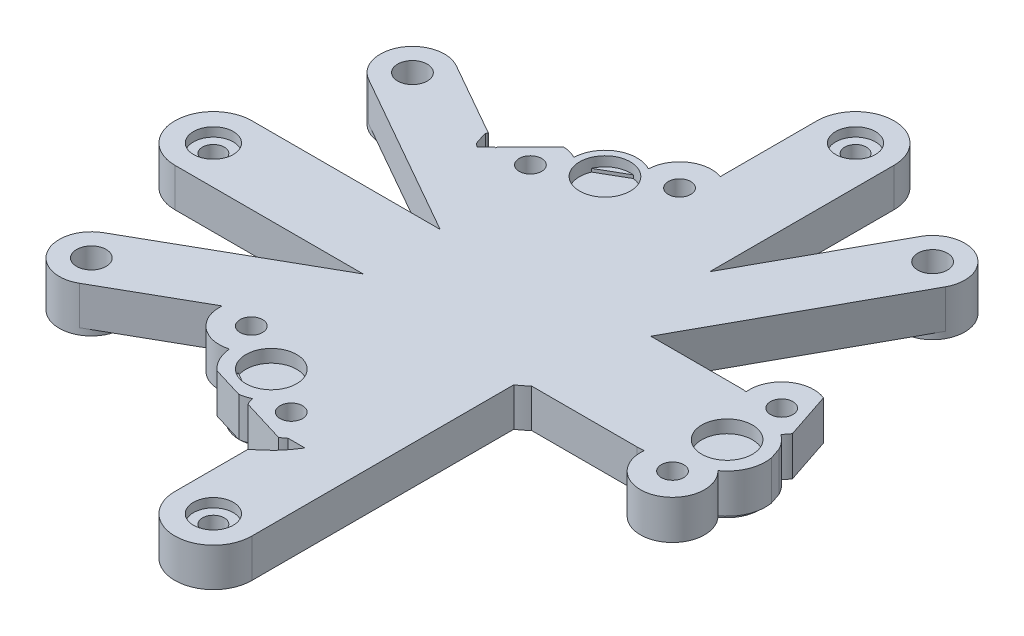
SolidWorks part; units mm, degrees
other "Fixed Star Plate Left"
ref_plane "Front Plane" through (0, 0, 0) normal (0, 0, 1) x (1, 0, 0)
ref_plane "Top Plane" through (0, 0, 0) normal (0, 1, 0) x (1, 0, 0)
ref_plane "Right Plane" through (0, 0, 0) normal (1, 0, 0) x (0, 0, -1)
sketch3d "Base Outline Sketch datum points"
  point P0 (0, 71, 0)
  point P1 (10, 71, 0)
  point P2 (0, 71, -10)
ref_plane "Base Outline Sketch plane" through (0, 71, 0) normal (0, 1, 0) x (1, 0, 0)
sketch "Base Outline Sketch" plane through (0, 71, 0) normal (0, 1, 0) x (1, 0, 0)
  line L0 (-32.2917, 8) -> (-46.1853, 8)
  line L1 (-24.4227, 13.1376) -> (-22.0154, 5.909)
  line L2 (-20.9711, 2.7735) -> (-20.3706, 0.9703)
  line L3 (-48.7418, -8) -> (-32.2917, -8)
  line L4 (-50.2917, -50) -> (-50.2917, -9.2195)
  line L5 (-62.2917, -38.6002) -> (-62.2917, -50)
  line L6 (-58.0273, -34) -> (-60.6452, -34)
  line L7 (-61.5389, -34.6217) -> (-68.3642, -32.542)
  line L8 (-70.4166, -31.9166) -> (-75.3281, -30.42)
  line L9 (-97.8216, -29.3473) -> (-83.633, -21.2856)
  line L10 (-76.9729, -6) -> (-102.7617, -20.6527)
  line L11 (-106.2917, -6) -> (-76.9729, -6)
  line L12 (-76.9729, 6) -> (-106.2917, 6)
  line L13 (-102.7617, 20.6527) -> (-76.9729, 6)
  line L14 (-86.2562, 22.776) -> (-97.8216, 29.3473)
  line L15 (-86.2562, 22.776) -> (-86.3054, 22.6772)
  line L16 (-86.3054, 22.6772) -> (-86.3838, 22.4486)
  line L17 (-85.7572, 20.4132) -> (-85.2034, 19.9887)
  line L18 (-85.2034, 19.9887) -> (-83.8108, 21.3866)
  line L19 (-83.633, 21.2856) -> (-83.8108, 21.3866)
  line L20 (-83.6495, 21.5484) -> (-78.4893, 26.7281)
  line L21 (-62.2917, 50) -> (-62.2917, 34.9546)
  line L22 (-50.2917, 21.2843) -> (-50.2917, 50)
  line L23 (-38.6727, 42.4096) -> (-50.2917, 21.2843)
  line L24 (-46.1853, 8) -> (-29.9106, 37.5904)
  circle A0 centre (-71.2917, -25.9808) radius 3.95
  circle A1 centre (-63.9304, -30.2308) radius 1.75
  circle A2 centre (-26.2917, 0) radius 3.95
  circle A3 centre (-56.2917, -50) radius 3.1
  circle A4 centre (-26.2917, -8.5) radius 1.75
  circle A5 centre (-78.6529, -21.7308) radius 1.75
  circle A6 centre (-100.2917, -25) radius 2.3
  circle A7 centre (-71.2917, 25.9808) radius 3.95
  circle A8 centre (-34.2917, 40) radius 2.3
  circle A9 centre (-26.2917, 8.5) radius 1.75
  circle A10 centre (-63.9304, 30.2308) radius 1.75
  circle A11 centre (-56.2917, 50) radius 3.1
  circle A12 centre (-78.6529, 21.7308) radius 1.75
  circle A13 centre (-106.2917, 0) radius 3.1
  circle A14 centre (-100.2917, 25) radius 2.3
  arc A15 (-31.2594, 7.9331) -> (-32.2917, 8) centre (-32.2917, 0) ccw
  arc A16 (-24.4227, 13.1376) -> (-31.2594, 7.9331) centre (-26.2917, 8.5) ccw
  arc A17 (-22.8248, 4.8971) -> (-22.0154, 5.909) centre (-26.2917, 8.5) ccw
  arc A18 (-20.9711, 2.7735) -> (-22.8248, 4.8971) centre (-26.2917, 0) ccw
  arc A19 (-22.8248, -4.8971) -> (-20.3706, 0.9703) centre (-26.2917, 0) ccw
  arc A20 (-31.2594, -7.9331) -> (-22.8248, -4.8971) centre (-26.2917, -8.5) ccw
  arc A21 (-32.2917, -8) -> (-31.2594, -7.9331) centre (-32.2917, 0) ccw
  arc A22 (-50.2917, -9.2195) -> (-48.7418, -8) centre (-56.2917, 0) ccw
  arc A23 (-62.2917, -50) -> (-50.2917, -50) centre (-56.2917, -50) ccw
  arc A24 (-62.2917, -38.6002) -> (-58.0273, -34) centre (-71.2917, -25.9808) ccw
  arc A25 (-61.5389, -34.6217) -> (-60.6452, -34) centre (-63.9304, -30.2308) ccw
  arc A26 (-68.7841, -31.4316) -> (-68.3642, -32.542) centre (-63.9304, -30.2308) ccw
  arc A27 (-70.4166, -31.9166) -> (-68.7841, -31.4316) centre (-71.2917, -25.9808) ccw
  arc A28 (-77.266, -26.5346) -> (-75.3281, -30.42) centre (-71.2917, -25.9808) ccw
  arc A29 (-83.633, -21.2856) -> (-77.266, -26.5346) centre (-78.6529, -21.7308) ccw
  arc A30 (-100.2917, -30) -> (-97.8216, -29.3473) centre (-100.2917, -25) ccw
  arc A31 (-102.7617, -20.6527) -> (-100.2917, -30) centre (-100.2917, -25) ccw
  arc A32 (-106.2917, 6) -> (-106.2917, -6) centre (-106.2917, 0) ccw
  arc A33 (-97.8216, 29.3473) -> (-102.7617, 20.6527) centre (-100.2917, 25) ccw
  arc A34 (-86.3838, 22.4486) -> (-85.7572, 20.4132) centre (-71.2917, 25.9808) ccw
  arc A35 (-83.6495, 21.5484) -> (-83.633, 21.2856) centre (-78.6529, 21.7308) ccw
  arc A36 (-76.2892, 26.1368) -> (-78.4893, 26.7281) centre (-78.6529, 21.7308) ccw
  arc A37 (-68.928, 30.3868) -> (-76.2892, 26.1368) centre (-71.2917, 25.9808) ccw
  arc A38 (-68.7841, 31.4316) -> (-68.928, 30.3868) centre (-63.9304, 30.2308) ccw
  arc A39 (-62.2917, 34.9546) -> (-68.7841, 31.4316) centre (-63.9304, 30.2308) ccw
  arc A40 (-50.2917, 50) -> (-62.2917, 50) centre (-56.2917, 50) ccw
  arc A41 (-29.9106, 37.5904) -> (-38.6727, 42.4096) centre (-34.2917, 40) ccw
extrude "Base Outline" add sketch "Base Outline Sketch" against normal blind 1.4 separate body
sketch3d "Interface Profile 2 Sketch datum points"
  point P0 (0, 69.6, 0)
  point P1 (10, 69.6, 0)
  point P2 (0, 69.6, -10)
ref_plane "Interface Profile 2 Sketch plane" through (0, 69.6, 0) normal (0, 1, 0) x (1, 0, 0)
sketch "Interface Profile 2 Sketch" plane through (0, 69.6, 0) normal (0, 1, 0) x (1, 0, 0)
  line L0 (-32.2917, 8) -> (-46.1853, 8)
  line L1 (-24.4227, 13.1376) -> (-22.0154, 5.909)
  line L2 (-20.9711, 2.7735) -> (-20.3706, 0.9703)
  line L3 (-48.7418, -8) -> (-32.2917, -8)
  line L4 (-50.2917, -50) -> (-50.2917, -9.2195)
  line L5 (-62.2917, -38.6002) -> (-62.2917, -50)
  line L6 (-58.0273, -34) -> (-60.6452, -34)
  line L7 (-61.5389, -34.6217) -> (-68.3642, -32.542)
  line L8 (-70.4166, -31.9166) -> (-75.3281, -30.42)
  line L9 (-97.8216, -29.3473) -> (-83.633, -21.2856)
  line L10 (-76.9729, -6) -> (-102.7617, -20.6527)
  line L11 (-106.2917, -6) -> (-76.9729, -6)
  line L12 (-76.9729, 6) -> (-106.2917, 6)
  line L13 (-102.7617, 20.6527) -> (-76.9729, 6)
  line L14 (-86.2562, 22.776) -> (-97.8216, 29.3473)
  line L15 (-86.2562, 22.776) -> (-86.3054, 22.6772)
  line L16 (-86.3054, 22.6772) -> (-86.3838, 22.4486)
  line L17 (-85.7572, 20.4132) -> (-85.2034, 19.9887)
  line L18 (-85.2034, 19.9887) -> (-83.8108, 21.3866)
  line L19 (-83.633, 21.2856) -> (-83.8108, 21.3866)
  line L20 (-83.6495, 21.5484) -> (-78.4893, 26.7281)
  line L21 (-62.2917, 50) -> (-62.2917, 34.9546)
  line L22 (-50.2917, 21.2843) -> (-50.2917, 50)
  line L23 (-38.6727, 42.4096) -> (-50.2917, 21.2843)
  line L24 (-46.1853, 8) -> (-29.9106, 37.5904)
  circle A0 centre (-71.2917, -25.9808) radius 3.95
  circle A1 centre (-63.9304, -30.2308) radius 1.75
  circle A2 centre (-26.2917, 0) radius 3.95
  circle A3 centre (-56.2917, -50) radius 1.7
  circle A4 centre (-56.2917, 50) radius 1.7
  circle A5 centre (-106.2917, 0) radius 1.7
  circle A6 centre (-26.2917, -8.5) radius 1.75
  circle A7 centre (-78.6529, -21.7308) radius 1.75
  circle A8 centre (-100.2917, -25) radius 2.3
  circle A9 centre (-71.2917, 25.9808) radius 3.95
  circle A10 centre (-34.2917, 40) radius 2.3
  circle A11 centre (-26.2917, 8.5) radius 1.75
  circle A12 centre (-63.9304, 30.2308) radius 1.75
  circle A13 centre (-78.6529, 21.7308) radius 1.75
  circle A14 centre (-100.2917, 25) radius 2.3
  arc A15 (-31.2594, 7.9331) -> (-32.2917, 8) centre (-32.2917, 0) ccw
  arc A16 (-24.4227, 13.1376) -> (-31.2594, 7.9331) centre (-26.2917, 8.5) ccw
  arc A17 (-22.8248, 4.8971) -> (-22.0154, 5.909) centre (-26.2917, 8.5) ccw
  arc A18 (-20.9711, 2.7735) -> (-22.8248, 4.8971) centre (-26.2917, 0) ccw
  arc A19 (-22.8248, -4.8971) -> (-20.3706, 0.9703) centre (-26.2917, 0) ccw
  arc A20 (-31.2594, -7.9331) -> (-22.8248, -4.8971) centre (-26.2917, -8.5) ccw
  arc A21 (-32.2917, -8) -> (-31.2594, -7.9331) centre (-32.2917, 0) ccw
  arc A22 (-50.2917, -9.2195) -> (-48.7418, -8) centre (-56.2917, 0) ccw
  arc A23 (-62.2917, -50) -> (-50.2917, -50) centre (-56.2917, -50) ccw
  arc A24 (-62.2917, -38.6002) -> (-58.0273, -34) centre (-71.2917, -25.9808) ccw
  arc A25 (-61.5389, -34.6217) -> (-60.6452, -34) centre (-63.9304, -30.2308) ccw
  arc A26 (-68.7841, -31.4316) -> (-68.3642, -32.542) centre (-63.9304, -30.2308) ccw
  arc A27 (-70.4166, -31.9166) -> (-68.7841, -31.4316) centre (-71.2917, -25.9808) ccw
  arc A28 (-77.266, -26.5346) -> (-75.3281, -30.42) centre (-71.2917, -25.9808) ccw
  arc A29 (-83.633, -21.2856) -> (-77.266, -26.5346) centre (-78.6529, -21.7308) ccw
  arc A30 (-100.2917, -30) -> (-97.8216, -29.3473) centre (-100.2917, -25) ccw
  arc A31 (-102.7617, -20.6527) -> (-100.2917, -30) centre (-100.2917, -25) ccw
  arc A32 (-106.2917, 6) -> (-106.2917, -6) centre (-106.2917, 0) ccw
  arc A33 (-97.8216, 29.3473) -> (-102.7617, 20.6527) centre (-100.2917, 25) ccw
  arc A34 (-86.3838, 22.4486) -> (-85.7572, 20.4132) centre (-71.2917, 25.9808) ccw
  arc A35 (-83.6495, 21.5484) -> (-83.633, 21.2856) centre (-78.6529, 21.7308) ccw
  arc A36 (-76.2892, 26.1368) -> (-78.4893, 26.7281) centre (-78.6529, 21.7308) ccw
  arc A37 (-68.928, 30.3868) -> (-76.2892, 26.1368) centre (-71.2917, 25.9808) ccw
  arc A38 (-68.7841, 31.4316) -> (-68.928, 30.3868) centre (-63.9304, 30.2308) ccw
  arc A39 (-62.2917, 34.9546) -> (-68.7841, 31.4316) centre (-63.9304, 30.2308) ccw
  arc A40 (-50.2917, 50) -> (-62.2917, 50) centre (-56.2917, 50) ccw
  arc A41 (-29.9106, 37.5904) -> (-38.6727, 42.4096) centre (-34.2917, 40) ccw
extrude "Interface Profile 2" add sketch "Interface Profile 2 Sketch" against normal blind 0.1
sketch3d "Interface Profile 3 Sketch datum points"
  point P0 (0, 69.5, 0)
  point P1 (10, 69.5, 0)
  point P2 (0, 69.5, -10)
ref_plane "Interface Profile 3 Sketch plane" through (0, 69.5, 0) normal (0, 1, 0) x (1, 0, 0)
sketch "Interface Profile 3 Sketch" plane through (0, 69.5, 0) normal (0, 1, 0) x (1, 0, 0)
  line L0 (-70.8027, -29.9004) -> (-74.9306, -27.5171)
  line L1 (-23.1417, 2.3833) -> (-23.1417, -2.3833)
  line L2 (-74.9306, 27.5171) -> (-70.8027, 29.9004)
  line L3 (-32.2917, 8) -> (-46.1853, 8)
  line L4 (-24.4227, 13.1376) -> (-22.0154, 5.909)
  line L5 (-20.9711, 2.7735) -> (-20.3706, 0.9703)
  line L6 (-48.7418, -8) -> (-32.2917, -8)
  line L7 (-50.2917, -50) -> (-50.2917, -9.2195)
  line L8 (-62.2917, -38.6002) -> (-62.2917, -50)
  line L9 (-58.0273, -34) -> (-60.6452, -34)
  line L10 (-61.5389, -34.6217) -> (-68.3642, -32.542)
  line L11 (-70.4166, -31.9166) -> (-75.3281, -30.42)
  line L12 (-97.8216, -29.3473) -> (-83.633, -21.2856)
  line L13 (-76.9729, -6) -> (-102.7617, -20.6527)
  line L14 (-106.2917, -6) -> (-76.9729, -6)
  line L15 (-76.9729, 6) -> (-106.2917, 6)
  line L16 (-102.7617, 20.6527) -> (-76.9729, 6)
  line L17 (-86.2562, 22.776) -> (-97.8216, 29.3473)
  line L18 (-86.2562, 22.776) -> (-86.3054, 22.6772)
  line L19 (-86.3054, 22.6772) -> (-86.3838, 22.4486)
  line L20 (-85.7572, 20.4132) -> (-85.2034, 19.9887)
  line L21 (-85.2034, 19.9887) -> (-83.8108, 21.3866)
  line L22 (-83.633, 21.2856) -> (-83.8108, 21.3866)
  line L23 (-83.6495, 21.5484) -> (-78.4893, 26.7281)
  line L24 (-62.2917, 50) -> (-62.2917, 34.9546)
  line L25 (-50.2917, 21.2843) -> (-50.2917, 50)
  line L26 (-38.6727, 42.4096) -> (-50.2917, 21.2843)
  line L27 (-46.1853, 8) -> (-29.9106, 37.5904)
  arc A0 (-67.3417, -25.9808) -> (-70.8027, -29.9004) centre (-71.2917, -25.9808) cw
  arc A1 (-74.9306, -27.5171) -> (-67.3417, -25.9808) centre (-71.2917, -25.9808) cw
  circle A2 centre (-63.9304, -30.2308) radius 1.75
  arc A3 (-23.1417, -2.3833) -> (-23.1417, 2.3833) centre (-26.2917, 0) cw
  circle A4 centre (-56.2917, -50) radius 1.7
  circle A5 centre (-56.2917, 50) radius 1.7
  circle A6 centre (-106.2917, 0) radius 1.7
  circle A7 centre (-26.2917, -8.5) radius 1.75
  circle A8 centre (-78.6529, -21.7308) radius 1.75
  circle A9 centre (-100.2917, -25) radius 2.3
  arc A10 (-67.3417, 25.9808) -> (-74.9306, 27.5171) centre (-71.2917, 25.9808) cw
  arc A11 (-70.8027, 29.9004) -> (-67.3417, 25.9808) centre (-71.2917, 25.9808) cw
  circle A12 centre (-34.2917, 40) radius 2.3
  circle A13 centre (-26.2917, 8.5) radius 1.75
  circle A14 centre (-63.9304, 30.2308) radius 1.75
  circle A15 centre (-78.6529, 21.7308) radius 1.75
  circle A16 centre (-100.2917, 25) radius 2.3
  arc A17 (-31.2594, 7.9331) -> (-32.2917, 8) centre (-32.2917, 0) ccw
  arc A18 (-24.4227, 13.1376) -> (-31.2594, 7.9331) centre (-26.2917, 8.5) ccw
  arc A19 (-22.8248, 4.8971) -> (-22.0154, 5.909) centre (-26.2917, 8.5) ccw
  arc A20 (-20.9711, 2.7735) -> (-22.8248, 4.8971) centre (-26.2917, 0) ccw
  arc A21 (-22.8248, -4.8971) -> (-20.3706, 0.9703) centre (-26.2917, 0) ccw
  arc A22 (-31.2594, -7.9331) -> (-22.8248, -4.8971) centre (-26.2917, -8.5) ccw
  arc A23 (-32.2917, -8) -> (-31.2594, -7.9331) centre (-32.2917, 0) ccw
  arc A24 (-50.2917, -9.2195) -> (-48.7418, -8) centre (-56.2917, 0) ccw
  arc A25 (-62.2917, -50) -> (-50.2917, -50) centre (-56.2917, -50) ccw
  arc A26 (-62.2917, -38.6002) -> (-58.0273, -34) centre (-71.2917, -25.9808) ccw
  arc A27 (-61.5389, -34.6217) -> (-60.6452, -34) centre (-63.9304, -30.2308) ccw
  arc A28 (-68.7841, -31.4316) -> (-68.3642, -32.542) centre (-63.9304, -30.2308) ccw
  arc A29 (-70.4166, -31.9166) -> (-68.7841, -31.4316) centre (-71.2917, -25.9808) ccw
  arc A30 (-77.266, -26.5346) -> (-75.3281, -30.42) centre (-71.2917, -25.9808) ccw
  arc A31 (-83.633, -21.2856) -> (-77.266, -26.5346) centre (-78.6529, -21.7308) ccw
  arc A32 (-100.2917, -30) -> (-97.8216, -29.3473) centre (-100.2917, -25) ccw
  arc A33 (-102.7617, -20.6527) -> (-100.2917, -30) centre (-100.2917, -25) ccw
  arc A34 (-106.2917, 6) -> (-106.2917, -6) centre (-106.2917, 0) ccw
  arc A35 (-97.8216, 29.3473) -> (-102.7617, 20.6527) centre (-100.2917, 25) ccw
  arc A36 (-86.3838, 22.4486) -> (-85.7572, 20.4132) centre (-71.2917, 25.9808) ccw
  arc A37 (-83.6495, 21.5484) -> (-83.633, 21.2856) centre (-78.6529, 21.7308) ccw
  arc A38 (-76.2892, 26.1368) -> (-78.4893, 26.7281) centre (-78.6529, 21.7308) ccw
  arc A39 (-68.928, 30.3868) -> (-76.2892, 26.1368) centre (-71.2917, 25.9808) ccw
  arc A40 (-68.7841, 31.4316) -> (-68.928, 30.3868) centre (-63.9304, 30.2308) ccw
  arc A41 (-62.2917, 34.9546) -> (-68.7841, 31.4316) centre (-63.9304, 30.2308) ccw
  arc A42 (-50.2917, 50) -> (-62.2917, 50) centre (-56.2917, 50) ccw
  arc A43 (-29.9106, 37.5904) -> (-38.6727, 42.4096) centre (-34.2917, 40) ccw
extrude "Interface Profile 3" add sketch "Interface Profile 3 Sketch" against normal blind 0.5
sketch3d "Interface Profile 4 Sketch datum points"
  point P0 (0, 69, 0)
  point P1 (10, 69, 0)
  point P2 (0, 69, -10)
ref_plane "Interface Profile 4 Sketch plane" through (0, 69, 0) normal (0, 1, 0) x (1, 0, 0)
sketch "Interface Profile 4 Sketch" plane through (0, 69, 0) normal (0, 1, 0) x (1, 0, 0)
  line L0 (-32.2917, 8) -> (-46.1853, 8)
  line L1 (-24.4227, 13.1376) -> (-22.0154, 5.909)
  line L2 (-20.9711, 2.7735) -> (-20.3706, 0.9703)
  line L3 (-48.7418, -8) -> (-32.2917, -8)
  line L4 (-50.2917, -50) -> (-50.2917, -9.2195)
  line L5 (-62.2917, -38.6002) -> (-62.2917, -50)
  line L6 (-58.0273, -34) -> (-60.6452, -34)
  line L7 (-61.5389, -34.6217) -> (-68.3642, -32.542)
  line L8 (-70.4166, -31.9166) -> (-75.3281, -30.42)
  line L9 (-97.8216, -29.3473) -> (-83.633, -21.2856)
  line L10 (-76.9729, -6) -> (-102.7617, -20.6527)
  line L11 (-106.2917, -6) -> (-76.9729, -6)
  line L12 (-76.9729, 6) -> (-106.2917, 6)
  line L13 (-102.7617, 20.6527) -> (-76.9729, 6)
  line L14 (-86.2562, 22.776) -> (-97.8216, 29.3473)
  line L15 (-86.2562, 22.776) -> (-86.3054, 22.6772)
  line L16 (-86.3054, 22.6772) -> (-86.3838, 22.4486)
  line L17 (-85.7572, 20.4132) -> (-85.2034, 19.9887)
  line L18 (-85.2034, 19.9887) -> (-83.8108, 21.3866)
  line L19 (-83.633, 21.2856) -> (-83.8108, 21.3866)
  line L20 (-83.6495, 21.5484) -> (-78.4893, 26.7281)
  line L21 (-62.2917, 50) -> (-62.2917, 34.9546)
  line L22 (-50.2917, 21.2843) -> (-50.2917, 50)
  line L23 (-38.6727, 42.4096) -> (-50.2917, 21.2843)
  line L24 (-46.1853, 8) -> (-29.9106, 37.5904)
  circle A0 centre (-63.9304, -30.2308) radius 1.75
  circle A1 centre (-56.2917, -50) radius 1.7
  circle A2 centre (-56.2917, 50) radius 1.7
  circle A3 centre (-106.2917, 0) radius 1.7
  circle A4 centre (-26.2917, -8.5) radius 1.75
  circle A5 centre (-78.6529, -21.7308) radius 1.75
  circle A6 centre (-100.2917, -25) radius 2.3
  circle A7 centre (-34.2917, 40) radius 2.3
  circle A8 centre (-26.2917, 8.5) radius 1.75
  circle A9 centre (-63.9304, 30.2308) radius 1.75
  circle A10 centre (-78.6529, 21.7308) radius 1.75
  circle A11 centre (-100.2917, 25) radius 2.3
  arc A12 (-31.2594, 7.9331) -> (-32.2917, 8) centre (-32.2917, 0) ccw
  arc A13 (-24.4227, 13.1376) -> (-31.2594, 7.9331) centre (-26.2917, 8.5) ccw
  arc A14 (-22.8248, 4.8971) -> (-22.0154, 5.909) centre (-26.2917, 8.5) ccw
  arc A15 (-20.9711, 2.7735) -> (-22.8248, 4.8971) centre (-26.2917, 0) ccw
  arc A16 (-22.8248, -4.8971) -> (-20.3706, 0.9703) centre (-26.2917, 0) ccw
  arc A17 (-31.2594, -7.9331) -> (-22.8248, -4.8971) centre (-26.2917, -8.5) ccw
  arc A18 (-32.2917, -8) -> (-31.2594, -7.9331) centre (-32.2917, 0) ccw
  arc A19 (-50.2917, -9.2195) -> (-48.7418, -8) centre (-56.2917, 0) ccw
  arc A20 (-62.2917, -50) -> (-50.2917, -50) centre (-56.2917, -50) ccw
  arc A21 (-62.2917, -38.6002) -> (-58.0273, -34) centre (-71.2917, -25.9808) ccw
  arc A22 (-61.5389, -34.6217) -> (-60.6452, -34) centre (-63.9304, -30.2308) ccw
  arc A23 (-68.7841, -31.4316) -> (-68.3642, -32.542) centre (-63.9304, -30.2308) ccw
  arc A24 (-70.4166, -31.9166) -> (-68.7841, -31.4316) centre (-71.2917, -25.9808) ccw
  arc A25 (-77.266, -26.5346) -> (-75.3281, -30.42) centre (-71.2917, -25.9808) ccw
  arc A26 (-83.633, -21.2856) -> (-77.266, -26.5346) centre (-78.6529, -21.7308) ccw
  arc A27 (-100.2917, -30) -> (-97.8216, -29.3473) centre (-100.2917, -25) ccw
  arc A28 (-102.7617, -20.6527) -> (-100.2917, -30) centre (-100.2917, -25) ccw
  arc A29 (-106.2917, 6) -> (-106.2917, -6) centre (-106.2917, 0) ccw
  arc A30 (-97.8216, 29.3473) -> (-102.7617, 20.6527) centre (-100.2917, 25) ccw
  arc A31 (-86.3838, 22.4486) -> (-85.7572, 20.4132) centre (-71.2917, 25.9808) ccw
  arc A32 (-83.6495, 21.5484) -> (-83.633, 21.2856) centre (-78.6529, 21.7308) ccw
  arc A33 (-76.2892, 26.1368) -> (-78.4893, 26.7281) centre (-78.6529, 21.7308) ccw
  arc A34 (-68.928, 30.3868) -> (-76.2892, 26.1368) centre (-71.2917, 25.9808) ccw
  arc A35 (-68.7841, 31.4316) -> (-68.928, 30.3868) centre (-63.9304, 30.2308) ccw
  arc A36 (-62.2917, 34.9546) -> (-68.7841, 31.4316) centre (-63.9304, 30.2308) ccw
  arc A37 (-50.2917, 50) -> (-62.2917, 50) centre (-56.2917, 50) ccw
  arc A38 (-29.9106, 37.5904) -> (-38.6727, 42.4096) centre (-34.2917, 40) ccw
extrude "Interface Profile 4" add sketch "Interface Profile 4 Sketch" against normal blind 1.5
sketch3d "Interface Profile 5 Sketch datum points"
  point P0 (0, 67.5, 0)
  point P1 (10, 67.5, 0)
  point P2 (0, 67.5, -10)
ref_plane "Interface Profile 5 Sketch plane" through (0, 67.5, 0) normal (0, 1, 0) x (1, 0, 0)
sketch "Interface Profile 5 Sketch" plane through (0, 67.5, 0) normal (0, 1, 0) x (1, 0, 0)
  line L0 (-59.5825, -50) -> (-57.9371, -47.15)
  line L1 (-57.9371, -52.85) -> (-59.5825, -50)
  line L2 (-57.9371, -47.15) -> (-54.6462, -47.15)
  line L3 (-54.6462, 52.85) -> (-53.0008, 50)
  line L4 (-57.9371, 52.85) -> (-54.6462, 52.85)
  line L5 (-53.0008, 50) -> (-54.6462, 47.15)
  line L6 (-59.5825, 50) -> (-57.9371, 52.85)
  line L7 (-57.9371, 47.15) -> (-59.5825, 50)
  line L8 (-54.6462, 47.15) -> (-57.9371, 47.15)
  line L9 (-104.6462, 2.85) -> (-103.0008, 0)
  line L10 (-107.9371, 2.85) -> (-104.6462, 2.85)
  line L11 (-103.0008, 0) -> (-104.6462, -2.85)
  line L12 (-109.5825, 0) -> (-107.9371, 2.85)
  line L13 (-107.9371, -2.85) -> (-109.5825, 0)
  line L14 (-104.6462, -2.85) -> (-107.9371, -2.85)
  line L15 (-54.6462, -52.85) -> (-57.9371, -52.85)
  line L16 (-54.6462, -47.15) -> (-53.0008, -50)
  line L17 (-53.0008, -50) -> (-54.6462, -52.85)
  line L18 (-32.2917, 8) -> (-46.1853, 8)
  line L19 (-24.4227, 13.1376) -> (-22.0154, 5.909)
  line L20 (-20.9711, 2.7735) -> (-20.3706, 0.9703)
  line L21 (-48.7418, -8) -> (-32.2917, -8)
  line L22 (-50.2917, -50) -> (-50.2917, -9.2195)
  line L23 (-62.2917, -38.6002) -> (-62.2917, -50)
  line L24 (-58.0273, -34) -> (-60.6452, -34)
  line L25 (-61.5389, -34.6217) -> (-68.3642, -32.542)
  line L26 (-70.4166, -31.9166) -> (-75.3281, -30.42)
  line L27 (-97.8216, -29.3473) -> (-83.633, -21.2856)
  line L28 (-76.9729, -6) -> (-102.7617, -20.6527)
  line L29 (-106.2917, -6) -> (-76.9729, -6)
  line L30 (-76.9729, 6) -> (-106.2917, 6)
  line L31 (-102.7617, 20.6527) -> (-76.9729, 6)
  line L32 (-86.2562, 22.776) -> (-97.8216, 29.3473)
  line L33 (-86.2562, 22.776) -> (-86.3054, 22.6772)
  line L34 (-86.3054, 22.6772) -> (-86.3838, 22.4486)
  line L35 (-85.7572, 20.4132) -> (-85.2034, 19.9887)
  line L36 (-85.2034, 19.9887) -> (-83.8108, 21.3866)
  line L37 (-83.633, 21.2856) -> (-83.8108, 21.3866)
  line L38 (-83.6495, 21.5484) -> (-78.4893, 26.7281)
  line L39 (-62.2917, 50) -> (-62.2917, 34.9546)
  line L40 (-50.2917, 21.2843) -> (-50.2917, 50)
  line L41 (-38.6727, 42.4096) -> (-50.2917, 21.2843)
  line L42 (-46.1853, 8) -> (-29.9106, 37.5904)
  circle A0 centre (-63.9304, -30.2308) radius 1.75
  circle A1 centre (-26.2917, -8.5) radius 1.75
  circle A2 centre (-78.6529, -21.7308) radius 1.75
  circle A3 centre (-100.2917, -25) radius 2.3
  circle A4 centre (-34.2917, 40) radius 2.3
  circle A5 centre (-26.2917, 8.5) radius 1.75
  circle A6 centre (-63.9304, 30.2308) radius 1.75
  circle A7 centre (-78.6529, 21.7308) radius 1.75
  circle A8 centre (-100.2917, 25) radius 2.3
  arc A9 (-31.2594, 7.9331) -> (-32.2917, 8) centre (-32.2917, 0) ccw
  arc A10 (-24.4227, 13.1376) -> (-31.2594, 7.9331) centre (-26.2917, 8.5) ccw
  arc A11 (-22.8248, 4.8971) -> (-22.0154, 5.909) centre (-26.2917, 8.5) ccw
  arc A12 (-20.9711, 2.7735) -> (-22.8248, 4.8971) centre (-26.2917, 0) ccw
  arc A13 (-22.8248, -4.8971) -> (-20.3706, 0.9703) centre (-26.2917, 0) ccw
  arc A14 (-31.2594, -7.9331) -> (-22.8248, -4.8971) centre (-26.2917, -8.5) ccw
  arc A15 (-32.2917, -8) -> (-31.2594, -7.9331) centre (-32.2917, 0) ccw
  arc A16 (-50.2917, -9.2195) -> (-48.7418, -8) centre (-56.2917, 0) ccw
  arc A17 (-62.2917, -50) -> (-50.2917, -50) centre (-56.2917, -50) ccw
  arc A18 (-62.2917, -38.6002) -> (-58.0273, -34) centre (-71.2917, -25.9808) ccw
  arc A19 (-61.5389, -34.6217) -> (-60.6452, -34) centre (-63.9304, -30.2308) ccw
  arc A20 (-68.7841, -31.4316) -> (-68.3642, -32.542) centre (-63.9304, -30.2308) ccw
  arc A21 (-70.4166, -31.9166) -> (-68.7841, -31.4316) centre (-71.2917, -25.9808) ccw
  arc A22 (-77.266, -26.5346) -> (-75.3281, -30.42) centre (-71.2917, -25.9808) ccw
  arc A23 (-83.633, -21.2856) -> (-77.266, -26.5346) centre (-78.6529, -21.7308) ccw
  arc A24 (-100.2917, -30) -> (-97.8216, -29.3473) centre (-100.2917, -25) ccw
  arc A25 (-102.7617, -20.6527) -> (-100.2917, -30) centre (-100.2917, -25) ccw
  arc A26 (-106.2917, 6) -> (-106.2917, -6) centre (-106.2917, 0) ccw
  arc A27 (-97.8216, 29.3473) -> (-102.7617, 20.6527) centre (-100.2917, 25) ccw
  arc A28 (-86.3838, 22.4486) -> (-85.7572, 20.4132) centre (-71.2917, 25.9808) ccw
  arc A29 (-83.6495, 21.5484) -> (-83.633, 21.2856) centre (-78.6529, 21.7308) ccw
  arc A30 (-76.2892, 26.1368) -> (-78.4893, 26.7281) centre (-78.6529, 21.7308) ccw
  arc A31 (-68.928, 30.3868) -> (-76.2892, 26.1368) centre (-71.2917, 25.9808) ccw
  arc A32 (-68.7841, 31.4316) -> (-68.928, 30.3868) centre (-63.9304, 30.2308) ccw
  arc A33 (-62.2917, 34.9546) -> (-68.7841, 31.4316) centre (-63.9304, 30.2308) ccw
  arc A34 (-50.2917, 50) -> (-62.2917, 50) centre (-56.2917, 50) ccw
  arc A35 (-29.9106, 37.5904) -> (-38.6727, 42.4096) centre (-34.2917, 40) ccw
extrude "Interface Profile 5" add sketch "Interface Profile 5 Sketch" against normal blind 0.5
sketch3d "Interface Profile 6 Sketch datum points"
  point P0 (0, 67, 0)
  point P1 (10, 67, 0)
  point P2 (0, 67, -10)
ref_plane "Interface Profile 6 Sketch plane" through (0, 67, 0) normal (0, 1, 0) x (1, 0, 0)
sketch "Interface Profile 6 Sketch" plane through (0, 67, 0) normal (0, 1, 0) x (1, 0, 0)
  line L0 (-59.5825, -50) -> (-57.9371, -47.15)
  line L1 (-57.9371, -52.85) -> (-59.5825, -50)
  line L2 (-57.9371, -47.15) -> (-54.6462, -47.15)
  line L3 (-54.6462, 52.85) -> (-53.0008, 50)
  line L4 (-57.9371, 52.85) -> (-54.6462, 52.85)
  line L5 (-53.0008, 50) -> (-54.6462, 47.15)
  line L6 (-59.5825, 50) -> (-57.9371, 52.85)
  line L7 (-57.9371, 47.15) -> (-59.5825, 50)
  line L8 (-54.6462, 47.15) -> (-57.9371, 47.15)
  line L9 (-104.6462, 2.85) -> (-103.0008, 0)
  line L10 (-107.9371, 2.85) -> (-104.6462, 2.85)
  line L11 (-103.0008, 0) -> (-104.6462, -2.85)
  line L12 (-109.5825, 0) -> (-107.9371, 2.85)
  line L13 (-107.9371, -2.85) -> (-109.5825, 0)
  line L14 (-104.6462, -2.85) -> (-107.9371, -2.85)
  line L15 (-54.6462, -52.85) -> (-57.9371, -52.85)
  line L16 (-54.6462, -47.15) -> (-53.0008, -50)
  line L17 (-53.0008, -50) -> (-54.6462, -52.85)
  line L18 (-32.2917, 8) -> (-46.1853, 8)
  line L19 (-24.4227, 13.1376) -> (-22.0154, 5.909)
  line L20 (-20.9711, 2.7735) -> (-20.3706, 0.9703)
  line L21 (-48.7418, -8) -> (-32.2917, -8)
  line L22 (-50.2917, -50) -> (-50.2917, -9.2195)
  line L23 (-62.2917, -38.6002) -> (-62.2917, -50)
  line L24 (-58.0273, -34) -> (-60.6452, -34)
  line L25 (-61.5389, -34.6217) -> (-68.3642, -32.542)
  line L26 (-70.4166, -31.9166) -> (-75.3281, -30.42)
  line L27 (-97.8216, -29.3473) -> (-83.633, -21.2856)
  line L28 (-76.9729, -6) -> (-102.7617, -20.6527)
  line L29 (-106.2917, -6) -> (-76.9729, -6)
  line L30 (-76.9729, 6) -> (-106.2917, 6)
  line L31 (-102.7617, 20.6527) -> (-76.9729, 6)
  line L32 (-86.2562, 22.776) -> (-97.8216, 29.3473)
  line L33 (-86.2562, 22.776) -> (-86.3054, 22.6772)
  line L34 (-86.3054, 22.6772) -> (-86.3838, 22.4486)
  line L35 (-85.7572, 20.4132) -> (-85.2034, 19.9887)
  line L36 (-85.2034, 19.9887) -> (-83.8108, 21.3866)
  line L37 (-83.633, 21.2856) -> (-83.8108, 21.3866)
  line L38 (-83.6495, 21.5484) -> (-78.4893, 26.7281)
  line L39 (-62.2917, 50) -> (-62.2917, 34.9546)
  line L40 (-50.2917, 21.2843) -> (-50.2917, 50)
  line L41 (-38.6727, 42.4096) -> (-50.2917, 21.2843)
  line L42 (-46.1853, 8) -> (-29.9106, 37.5904)
  circle A0 centre (-63.9304, -30.2308) radius 1.1
  circle A1 centre (-26.2917, -8.5) radius 1.1
  circle A2 centre (-78.6529, -21.7308) radius 1.1
  circle A3 centre (-100.2917, -25) radius 2.3
  circle A4 centre (-34.2917, 40) radius 2.3
  circle A5 centre (-26.2917, 8.5) radius 1.1
  circle A6 centre (-63.9304, 30.2308) radius 1.1
  circle A7 centre (-78.6529, 21.7308) radius 1.1
  circle A8 centre (-100.2917, 25) radius 2.3
  arc A9 (-31.2594, 7.9331) -> (-32.2917, 8) centre (-32.2917, 0) ccw
  arc A10 (-24.4227, 13.1376) -> (-31.2594, 7.9331) centre (-26.2917, 8.5) ccw
  arc A11 (-22.8248, 4.8971) -> (-22.0154, 5.909) centre (-26.2917, 8.5) ccw
  arc A12 (-20.9711, 2.7735) -> (-22.8248, 4.8971) centre (-26.2917, 0) ccw
  arc A13 (-22.8248, -4.8971) -> (-20.3706, 0.9703) centre (-26.2917, 0) ccw
  arc A14 (-31.2594, -7.9331) -> (-22.8248, -4.8971) centre (-26.2917, -8.5) ccw
  arc A15 (-32.2917, -8) -> (-31.2594, -7.9331) centre (-32.2917, 0) ccw
  arc A16 (-50.2917, -9.2195) -> (-48.7418, -8) centre (-56.2917, 0) ccw
  arc A17 (-62.2917, -50) -> (-50.2917, -50) centre (-56.2917, -50) ccw
  arc A18 (-62.2917, -38.6002) -> (-58.0273, -34) centre (-71.2917, -25.9808) ccw
  arc A19 (-61.5389, -34.6217) -> (-60.6452, -34) centre (-63.9304, -30.2308) ccw
  arc A20 (-68.7841, -31.4316) -> (-68.3642, -32.542) centre (-63.9304, -30.2308) ccw
  arc A21 (-70.4166, -31.9166) -> (-68.7841, -31.4316) centre (-71.2917, -25.9808) ccw
  arc A22 (-77.266, -26.5346) -> (-75.3281, -30.42) centre (-71.2917, -25.9808) ccw
  arc A23 (-83.633, -21.2856) -> (-77.266, -26.5346) centre (-78.6529, -21.7308) ccw
  arc A24 (-100.2917, -30) -> (-97.8216, -29.3473) centre (-100.2917, -25) ccw
  arc A25 (-102.7617, -20.6527) -> (-100.2917, -30) centre (-100.2917, -25) ccw
  arc A26 (-106.2917, 6) -> (-106.2917, -6) centre (-106.2917, 0) ccw
  arc A27 (-97.8216, 29.3473) -> (-102.7617, 20.6527) centre (-100.2917, 25) ccw
  arc A28 (-86.3838, 22.4486) -> (-85.7572, 20.4132) centre (-71.2917, 25.9808) ccw
  arc A29 (-83.6495, 21.5484) -> (-83.633, 21.2856) centre (-78.6529, 21.7308) ccw
  arc A30 (-76.2892, 26.1368) -> (-78.4893, 26.7281) centre (-78.6529, 21.7308) ccw
  arc A31 (-68.928, 30.3868) -> (-76.2892, 26.1368) centre (-71.2917, 25.9808) ccw
  arc A32 (-68.7841, 31.4316) -> (-68.928, 30.3868) centre (-63.9304, 30.2308) ccw
  arc A33 (-62.2917, 34.9546) -> (-68.7841, 31.4316) centre (-63.9304, 30.2308) ccw
  arc A34 (-50.2917, 50) -> (-62.2917, 50) centre (-56.2917, 50) ccw
  arc A35 (-29.9106, 37.5904) -> (-38.6727, 42.4096) centre (-34.2917, 40) ccw
extrude "Interface Profile 6" add sketch "Interface Profile 6 Sketch" against normal blind 1.3
sketch3d "Interface Profile 7 Sketch datum points"
  point P0 (0, 65.7, 0)
  point P1 (10, 65.7, 0)
  point P2 (0, 65.7, -10)
ref_plane "Interface Profile 7 Sketch plane" through (0, 65.7, 0) normal (0, 1, 0) x (1, 0, 0)
sketch "Interface Profile 7 Sketch" plane through (0, 65.7, 0) normal (0, 1, 0) x (1, 0, 0)
  line L0 (-59.5825, -50) -> (-57.9371, -47.15)
  line L1 (-57.9371, -52.85) -> (-59.5825, -50)
  line L2 (-57.9371, -47.15) -> (-54.6462, -47.15)
  line L3 (-54.6462, 52.85) -> (-53.0008, 50)
  line L4 (-57.9371, 52.85) -> (-54.6462, 52.85)
  line L5 (-53.0008, 50) -> (-54.6462, 47.15)
  line L6 (-59.5825, 50) -> (-57.9371, 52.85)
  line L7 (-57.9371, 47.15) -> (-59.5825, 50)
  line L8 (-54.6462, 47.15) -> (-57.9371, 47.15)
  line L9 (-104.6462, 2.85) -> (-103.0008, 0)
  line L10 (-107.9371, 2.85) -> (-104.6462, 2.85)
  line L11 (-103.0008, 0) -> (-104.6462, -2.85)
  line L12 (-109.5825, 0) -> (-107.9371, 2.85)
  line L13 (-107.9371, -2.85) -> (-109.5825, 0)
  line L14 (-104.6462, -2.85) -> (-107.9371, -2.85)
  line L15 (-54.6462, -52.85) -> (-57.9371, -52.85)
  line L16 (-54.6462, -47.15) -> (-53.0008, -50)
  line L17 (-53.0008, -50) -> (-54.6462, -52.85)
  line L18 (-32.2917, 8) -> (-46.1853, 8)
  line L19 (-24.4227, 13.1376) -> (-22.0154, 5.909)
  line L20 (-20.9711, 2.7735) -> (-20.3706, 0.9703)
  line L21 (-48.7418, -8) -> (-32.2917, -8)
  line L22 (-50.2917, -50) -> (-50.2917, -9.2195)
  line L23 (-62.2917, -38.6002) -> (-62.2917, -50)
  line L24 (-58.0273, -34) -> (-60.6452, -34)
  line L25 (-61.5389, -34.6217) -> (-68.3642, -32.542)
  line L26 (-70.4166, -31.9166) -> (-75.3281, -30.42)
  line L27 (-97.8216, -29.3473) -> (-83.633, -21.2856)
  line L28 (-76.9729, -6) -> (-102.7617, -20.6527)
  line L29 (-106.2917, -6) -> (-76.9729, -6)
  line L30 (-76.9729, 6) -> (-106.2917, 6)
  line L31 (-102.7617, 20.6527) -> (-76.9729, 6)
  line L32 (-86.2562, 22.776) -> (-97.8216, 29.3473)
  line L33 (-86.2562, 22.776) -> (-86.3054, 22.6772)
  line L34 (-86.3054, 22.6772) -> (-86.3838, 22.4486)
  line L35 (-85.7572, 20.4132) -> (-85.2034, 19.9887)
  line L36 (-85.2034, 19.9887) -> (-83.8108, 21.3866)
  line L37 (-83.633, 21.2856) -> (-83.8108, 21.3866)
  line L38 (-83.6495, 21.5484) -> (-78.4893, 26.7281)
  line L39 (-62.2917, 50) -> (-62.2917, 34.9546)
  line L40 (-50.2917, 21.2843) -> (-50.2917, 50)
  line L41 (-38.6727, 42.4096) -> (-50.2917, 21.2843)
  line L42 (-46.1853, 8) -> (-29.9106, 37.5904)
  circle A0 centre (-100.2917, -25) radius 2.3
  circle A1 centre (-34.2917, 40) radius 2.3
  circle A2 centre (-100.2917, 25) radius 2.3
  arc A3 (-31.2594, 7.9331) -> (-32.2917, 8) centre (-32.2917, 0) ccw
  arc A4 (-24.4227, 13.1376) -> (-31.2594, 7.9331) centre (-26.2917, 8.5) ccw
  arc A5 (-22.8248, 4.8971) -> (-22.0154, 5.909) centre (-26.2917, 8.5) ccw
  arc A6 (-20.9711, 2.7735) -> (-22.8248, 4.8971) centre (-26.2917, 0) ccw
  arc A7 (-22.8248, -4.8971) -> (-20.3706, 0.9703) centre (-26.2917, 0) ccw
  arc A8 (-31.2594, -7.9331) -> (-22.8248, -4.8971) centre (-26.2917, -8.5) ccw
  arc A9 (-32.2917, -8) -> (-31.2594, -7.9331) centre (-32.2917, 0) ccw
  arc A10 (-50.2917, -9.2195) -> (-48.7418, -8) centre (-56.2917, 0) ccw
  arc A11 (-62.2917, -50) -> (-50.2917, -50) centre (-56.2917, -50) ccw
  arc A12 (-62.2917, -38.6002) -> (-58.0273, -34) centre (-71.2917, -25.9808) ccw
  arc A13 (-61.5389, -34.6217) -> (-60.6452, -34) centre (-63.9304, -30.2308) ccw
  arc A14 (-68.7841, -31.4316) -> (-68.3642, -32.542) centre (-63.9304, -30.2308) ccw
  arc A15 (-70.4166, -31.9166) -> (-68.7841, -31.4316) centre (-71.2917, -25.9808) ccw
  arc A16 (-77.266, -26.5346) -> (-75.3281, -30.42) centre (-71.2917, -25.9808) ccw
  arc A17 (-83.633, -21.2856) -> (-77.266, -26.5346) centre (-78.6529, -21.7308) ccw
  arc A18 (-100.2917, -30) -> (-97.8216, -29.3473) centre (-100.2917, -25) ccw
  arc A19 (-102.7617, -20.6527) -> (-100.2917, -30) centre (-100.2917, -25) ccw
  arc A20 (-106.2917, 6) -> (-106.2917, -6) centre (-106.2917, 0) ccw
  arc A21 (-97.8216, 29.3473) -> (-102.7617, 20.6527) centre (-100.2917, 25) ccw
  arc A22 (-86.3838, 22.4486) -> (-85.7572, 20.4132) centre (-71.2917, 25.9808) ccw
  arc A23 (-83.6495, 21.5484) -> (-83.633, 21.2856) centre (-78.6529, 21.7308) ccw
  arc A24 (-76.2892, 26.1368) -> (-78.4893, 26.7281) centre (-78.6529, 21.7308) ccw
  arc A25 (-68.928, 30.3868) -> (-76.2892, 26.1368) centre (-71.2917, 25.9808) ccw
  arc A26 (-68.7841, 31.4316) -> (-68.928, 30.3868) centre (-63.9304, 30.2308) ccw
  arc A27 (-62.2917, 34.9546) -> (-68.7841, 31.4316) centre (-63.9304, 30.2308) ccw
  arc A28 (-50.2917, 50) -> (-62.2917, 50) centre (-56.2917, 50) ccw
  arc A29 (-29.9106, 37.5904) -> (-38.6727, 42.4096) centre (-34.2917, 40) ccw
extrude "Interface Profile 7" add sketch "Interface Profile 7 Sketch" against normal blind 0.7
sketch3d "Interface Profile 8 Sketch datum points"
  point P0 (0, 65, 0)
  point P1 (10, 65, 0)
  point P2 (0, 65, -10)
ref_plane "Interface Profile 8 Sketch plane" through (0, 65, 0) normal (0, 1, 0) x (1, 0, 0)
sketch "Interface Profile 8 Sketch" plane through (0, 65, 0) normal (0, 1, 0) x (1, 0, 0)
  line L0 (-24.4227, 13.1376) -> (-22.0154, 5.909)
  line L1 (-20.9711, 2.7735) -> (-20.3706, 0.9703)
  line L2 (-61.5389, -34.6217) -> (-68.3642, -32.542)
  line L3 (-70.4166, -31.9166) -> (-75.3281, -30.42)
  line L4 (-83.6495, 21.5484) -> (-78.4893, 26.7281)
  arc A0 (-65.3173, -25.4269) -> (-73.7992, -20.5299) centre (-71.2917, -25.9808) ccw
  arc A1 (-61.5389, -34.6217) -> (-65.3173, -25.4269) centre (-63.9304, -30.2308) ccw
  arc A2 (-73.7992, -20.5299) -> (-77.266, -26.5346) centre (-78.6529, -21.7308) ccw
  arc A3 (-66.2941, 25.8247) -> (-65.3173, 25.4269) centre (-63.9304, 30.2308) ccw
  arc A4 (-73.6553, 21.5747) -> (-66.2941, 25.8247) centre (-71.2917, 25.9808) ccw
  arc A5 (-65.3173, 25.4269) -> (-68.7841, 31.4316) centre (-63.9304, 30.2308) ccw
  arc A6 (-29.7585, 4.8971) -> (-29.7585, -4.8971) centre (-26.2917, 0) ccw
  arc A7 (-24.4227, 13.1376) -> (-29.7585, 4.8971) centre (-26.2917, 8.5) ccw
  arc A8 (-29.7585, -4.8971) -> (-22.8248, -4.8971) centre (-26.2917, -8.5) ccw
  circle A9 centre (-100.2917, -25) radius 2.3
  circle A10 centre (-34.2917, 40) radius 2.3
  circle A11 centre (-100.2917, 25) radius 2.3
  arc A12 (-22.8248, 4.8971) -> (-22.0154, 5.909) centre (-26.2917, 8.5) ccw
  arc A13 (-20.9711, 2.7735) -> (-22.8248, 4.8971) centre (-26.2917, 0) ccw
  arc A14 (-22.8248, -4.8971) -> (-20.3706, 0.9703) centre (-26.2917, 0) ccw
  arc A15 (-68.7841, -31.4316) -> (-68.3642, -32.542) centre (-63.9304, -30.2308) ccw
  arc A16 (-70.4166, -31.9166) -> (-68.7841, -31.4316) centre (-71.2917, -25.9808) ccw
  arc A17 (-77.266, -26.5346) -> (-75.3281, -30.42) centre (-71.2917, -25.9808) ccw
  arc A18 (-100.2917, -30) -> (-97.8216, -29.3473) centre (-100.2917, -25) ccw
  arc A19 (-97.8216, -29.3473) -> (-100.2917, -30) centre (-100.2917, -25) ccw
  circle A20 centre (-100.2917, 25) radius 5
  arc A21 (-83.6495, 21.5484) -> (-73.6553, 21.5747) centre (-78.6529, 21.7308) ccw
  arc A22 (-76.2892, 26.1368) -> (-78.4893, 26.7281) centre (-78.6529, 21.7308) ccw
  arc A23 (-68.928, 30.3868) -> (-76.2892, 26.1368) centre (-71.2917, 25.9808) ccw
  arc A24 (-68.7841, 31.4316) -> (-68.928, 30.3868) centre (-63.9304, 30.2308) ccw
  circle A25 centre (-34.2917, 40) radius 5
extrude "Interface Profile 8" add sketch "Interface Profile 8 Sketch" against normal blind 0.1
sketch3d "Interface Profile 9 Sketch datum points"
  point P0 (0, 64.9, 0)
  point P1 (10, 64.9, 0)
  point P2 (0, 64.9, -10)
ref_plane "Interface Profile 9 Sketch plane" through (0, 64.9, 0) normal (0, 1, 0) x (1, 0, 0)
sketch "Interface Profile 9 Sketch" plane through (0, 64.9, 0) normal (0, 1, 0) x (1, 0, 0)
  circle A0 centre (-71.2917, -25.9808) radius 5
  circle A1 centre (-26.2917, 0) radius 5
  circle A2 centre (-100.2917, -25) radius 2.3
  circle A3 centre (-34.2917, 40) radius 2.3
  circle A4 centre (-100.2917, 25) radius 2.3
  arc A5 (-100.2917, -30) -> (-97.8216, -29.3473) centre (-100.2917, -25) ccw
  arc A6 (-97.8216, -29.3473) -> (-100.2917, -30) centre (-100.2917, -25) ccw
  circle A7 centre (-100.2917, 25) radius 5
  circle A8 centre (-71.2917, 25.9808) radius 5
  circle A9 centre (-34.2917, 40) radius 5
extrude "Interface Profile 9" add sketch "Interface Profile 9 Sketch" against normal blind 0.9
